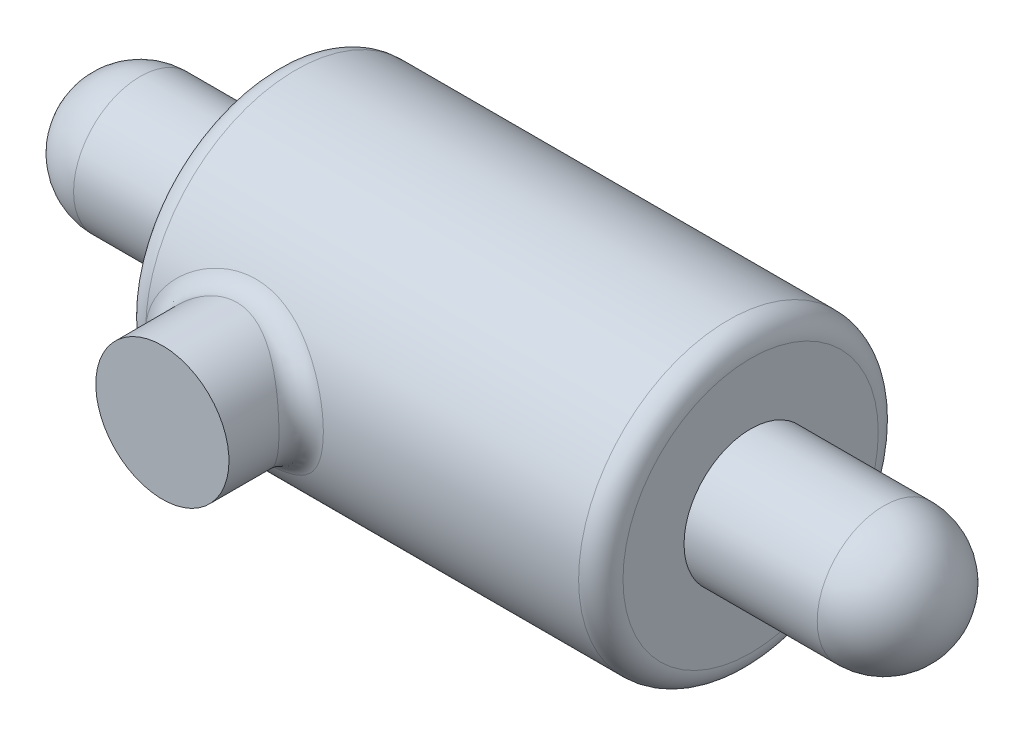
SolidWorks part; units mm, degrees
material "Sheet Moulding Compound"
ref_plane "Front Plane" through (0, 0, 0) normal (0, 0, 1) x (1, 0, 0)
ref_plane "Top Plane" through (0, 0, 0) normal (0, 1, 0) x (1, 0, 0)
ref_plane "Right Plane" through (0, 0, 0) normal (1, 0, 0) x (0, 0, -1)
sketch "Sketch1" plane through (0, 0, 0) normal (0, 1, 0) x (1, 0, 0)
  line L1 (-47.3109, 0) -> (-4.3109, 0)
  line L2 (-47.3109, 0) -> (-47.3109, -13.5)
  line L3 (-47.3109, -13.5) -> (-4.3109, -13.5)
  line L4 (-4.3109, 0) -> (-4.3109, -13.5)
revolve "Revolve1" add sketch "Sketch1" angle 360 about L1
sketch "Sketch4" plane through (0, 0, 0) normal (0, 0, 1) x (1, 0, 0)
  line L0 (-47.3109, 13.5) -> (-47.3109, -13.5) construction
  line L1 (-4.3109, 13.5) -> (-47.3109, 13.5) construction
  circle A0 centre (-37.3109, 0) radius 6
  dimension "D1" = 12
  dimension "D2" = 10
  dimension "D3" = 13.5
extrude "Boss-Extrude2" add sketch "Sketch4" along normal blind 20
sketch "Sketch5" plane through (-47.3109, 0, 0) normal (-1, 0, 0) x (0, 0, 1)
  circle A1 centre (0, 0) radius 6
  dimension "D1" = 12
extrude "Boss-Extrude3" add sketch "Sketch5" along normal blind 18
fillet "Fillet1" radius 6 1 edges at (-65.3109, 0, 6)
sketch "Sketch6" plane through (-4.3109, 0, 0) normal (1, 0, 0) x (0, 0, -1)
  circle A0 centre (0, 0) radius 6
  dimension "D1" = 12
extrude "Boss-Extrude4" add sketch "Sketch6" along normal blind 18
fillet "Fillet2" radius 6 1 edges at (13.6891, 0, -6)
fillet "Fillet3" radius 2 2 edges at (-4.3109, 0, 13.5) (-47.3109, 0, 13.5)
fillet "Fillet4" radius 2 1 edges at (-43.2628, 0.7581, 13.4787)
